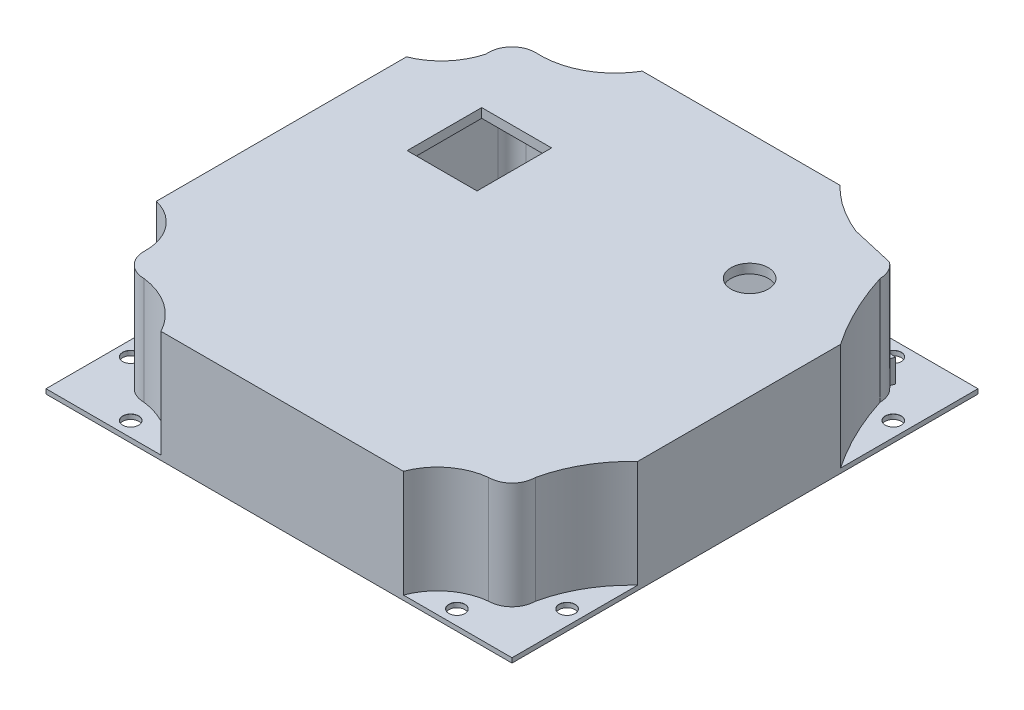
SolidWorks part; units mm, degrees
note: The reader was unsure of these and kept them because the rebuilt part matched: shared geometry of "Sketch21<3>".
material "6061 Alloy"
ref_plane "Front Plane" through (0, 0, 0) normal (0, 0, 1) x (1, 0, 0)
ref_plane "Top Plane" through (0, 0, 0) normal (0, 1, 0) x (1, 0, 0)
ref_plane "Right Plane" through (0, 0, 0) normal (1, 0, 0) x (0, 0, -1)
sketch "Sketch1" plane through (0, 0, 0) normal (0, 1, 0) x (1, 0, 0)
  line L1 (-50, -50) -> (50, -50)
  line L2 (-50, -50) -> (-50, 50)
  line L3 (-50, 50) -> (50, 50)
  line L4 (50, -50) -> (50, 50)
  line L5 (-50, -50) -> (50, 50) construction
  line L6 (-50, 50) -> (50, -50) construction
extrude "Boss-Extrude3" add sketch "Sketch1" along normal blind 6.35
sketch "Sketch8" plane through (0, 6.35, 0) normal (0, 1, 0) x (1, 0, 0)
  line L0 (-50, -50) -> (-39.5, -50)
  line L1 (-50, -50) -> (50, -50) construction
  line L2 (-39.5, -50) -> (-39.5, -39.5)
  line L3 (50, -50) -> (39.5, -50)
  line L4 (39.5, -50) -> (39.5, -39.5)
  line L5 (50, 50) -> (39.5, 50)
  line L6 (-50, 50) -> (50, 50) construction
  line L7 (39.5, 50) -> (39.5, 39.5)
  line L8 (-50, 50) -> (-39.5, 50)
  line L9 (-50, -50) -> (-50, 50) construction
  line L10 (-39.5, 50) -> (-39.5, 39.5)
sketch "Sketch13" plane through (0, 6.35, 0) normal (0, 1, 0) x (1, 0, 0)
  line L1 (-50, -50) -> (-35, -50)
  line L2 (-50, -50) -> (50, -50) construction
  line L3 (-35, -50) -> (-35, -46.825)
  line L4 (-50, -50) -> (-50, -35)
  line L5 (-50, -50) -> (-50, 50) construction
  line L6 (-50, -35) -> (-46.825, -35)
  line L7 (-50, 50) -> (-35, 50)
  line L8 (-50, 50) -> (50, 50) construction
  line L9 (-35, 50) -> (-35, 46.825)
  line L10 (-50, 50) -> (-50, 35)
  line L11 (-50, 35) -> (-46.825, 35)
  line L13 (50, 50) -> (35, 50)
  line L14 (35, 50) -> (35, 46.825)
  line L15 (50, 50) -> (50, 35)
  line L16 (50, -50) -> (50, 50) construction
  line L17 (50, 35) -> (46.825, 35)
  line L18 (50, -50) -> (50, -35)
  line L19 (50, -35) -> (46.825, -35)
  line L20 (50, -50) -> (35, -50)
  line L21 (35, -50) -> (35, -46.825)
hole_wizard "M3 Clearance Hole1" positions "Sketch17" profile "Sketch18" hole size "M3" standard "ANSI Metric" end condition through all
sketch "Sketch17" plane through (0, 6.35, 0) normal (0, 1, 0) x (1, 0, 0)
  point P0 (-46.825, 35)
  point P3 (-35, 46.825)
  point P6 (35, 46.825)
  point P9 (46.825, 35)
  point P12 (46.825, -35)
  point P15 (35, -46.825)
  point P18 (-35, -46.825)
  point P21 (-46.825, -35)
sketch "Sketch18" plane through (-46.825, 6.35, -35) normal (1, 0, 0) x (0, 0, 1)
  line L0 (0, 0) -> (0, 6.35)
  line L1 (0, 6.35) -> (1.7, 6.35)
  line L2 (1.7, 6.35) -> (1.7, 0.025)
  line L3 (1.7, 0.025) -> (1.725, 0)
  line L5 (1.725, 0) -> (0, 0)
  line L6 (-1.7, 0.025) -> (-1.725, 0) construction
  line L11 (0, -6.35) -> (0, 107.95) construction
  dimension "Thru Hole Dia." = 3.4
  dimension "Thru Hole Depth" = 6.35
  dimension "Near C'Sink Dia." = 3.45
  dimension "Near C'Sink Angle" = 90
sketch "Sketch19" plane through (0, 6.35, 0) normal (0, 1, 0) x (1, 0, 0)
  line L1 (-37, -40) -> (37, -40)
  line L2 (-40, -37) -> (-40, 37)
  line L3 (-37, 40) -> (37, 40)
  line L4 (40, -37) -> (40, 37)
  line L5 (-40, -40) -> (40, 40) construction
  line L6 (-40, 40) -> (40, -40) construction
  arc A0 (-37, -40) -> (-40, -37) centre (-37, -37) cw
  arc A1 (40, -37) -> (37, -40) centre (37, -37) cw
  arc A2 (37, 40) -> (40, 37) centre (37, 37) cw
  arc A3 (-37, 40) -> (-40, 37) centre (-37, 37) ccw
  point P0 (0, 0)
  dimension "D1" = 3
extrude "Cut-Extrude1" cut sketch "Sketch19" against normal blind 10
sketch "Sketch20" plane through (0, 6.35, -6.35) normal (0, -1, 0) x (1, 0, 0)
  line L2 (6.2004, 36.4882) -> (20.6711, -21.587) construction
  line L4 (20.6711, -21.587) -> (17.5137, -18.2418) construction
  line L5 (1.6004, 36.4882) -> (1.6004, 46.35)
  line L6 (-37, 46.35) -> (37, 46.35) construction
  line L7 (10.8004, 36.4882) -> (10.8004, 46.35)
  line L8 (23.8395, -18.2522) -> (39.1213, -32.7713)
  line L9 (17.5038, -24.9228) -> (26.6951, -33.65)
  line L10 (37, -33.65) -> (-37, -33.65) construction
  line L18 (1.6004, 46.35) -> (1.6004, 51.4058)
  line L19 (1.6004, 51.4058) -> (10.8004, 51.4058)
  line L20 (10.8004, 51.4058) -> (10.8004, 46.35)
  line L21 (26.6951, -33.65) -> (30.5647, -36.8517)
  line L22 (30.5647, -36.8517) -> (40.2934, -35.6218)
  line L23 (40.2934, -35.6218) -> (39.1213, -32.7713)
  line L25 (1.6065, 36.2521) -> (6.2004, 36.4882) construction
  arc A1 (23.8395, -18.2522) -> (17.5038, -24.9228) centre (20.6711, -21.587) ccw
  arc A2 (1.6004, 36.4882) -> (10.8004, 36.4882) centre (6.2004, 36.4882) ccw
  circle A3 centre (20.6711, -21.587) radius 1.6
  circle A4 centre (6.2004, 36.4882) radius 1.6
  circle A9 centre (6.2004, 36.4882) radius 4.6 construction
  arc A10 (37, -33.65) -> (40, -30.65) centre (37, -30.65) ccw construction
  circle A11 centre (20.6711, -21.587) radius 4.6 construction
  dimension "D2" = 58.0752
  dimension "D5" = 3
extrude "Boss-Extrude4" add sketch "Sketch20" against normal blind 5 contours A3 | A4 | L20 L7 A2 L5 L18 L19 | L23 L8 A1 L9 L21 L22
sketch "Sketch21" plane through (0, 6.35, 0) normal (0, 1, 0) x (1, 0, 0)
  line L2 (40, -37) -> (40, 37) construction
  line L3 (26.6951, 40) -> (-37, 40) construction
  line L4 (-40, 37) -> (-40, -37) construction
  line L7 (40, -37) -> (40, 37)
  line L8 (26.6951, 40) -> (-37, 40)
  line L9 (-40, 37) -> (-40, -37)
  line L10 (-35.0509, 42) -> (-37, 42)
  line L11 (-42, 37) -> (-42, 36.3352)
  line L12 (40.2934, 41.9718) -> (39.1213, 39.1213) construction
  line L13 (30.5647, 43.2017) -> (39.9185, 41.0599)
  line L15 (-50, -50) -> (-50, 50) construction
  line L16 (-50, -50) -> (50, -50) construction
  line L17 (50, -50) -> (50, 50) construction
  line L18 (26.6951, 40) -> (30.5647, 43.2017) construction
  line L19 (-50, 50) -> (50, 50) construction
  line L20 (-22.05, 50) -> (20.3723, 50)
  line L22 (-37, -40) -> (37, -40)
  line L23 (50, 20.5088) -> (50, -23.0373)
  line L24 (26.6951, -50) -> (-25.3277, -50)
  line L25 (-50, -26.3149) -> (-50, 27.345)
  line L26 (-42, -36.1865) -> (-42, -37)
  line L27 (-42, 37) -> (-42, -37) construction
  line L28 (26.6951, 42) -> (-37, 42) construction
  line L29 (42, -37) -> (42, 37) construction
  line L30 (10.8004, -42) -> (37, -42) construction
  line L31 (-37, -42) -> (1.6004, -42) construction
  line L32 (26.6951, 40) -> (39.1213, 39.1213)
  line L35 (10.8004, -40) -> (37, -40) construction
  line L36 (-37, -40) -> (1.6004, -40) construction
  arc A0 (-40, -37) -> (-37, -40) centre (-37, -37) ccw construction
  arc A1 (37, -40) -> (40, -37) centre (37, -37) ccw construction
  arc A2 (40, 37) -> (39.1213, 39.1213) centre (37, 37) ccw construction
  arc A3 (-37, 40) -> (-40, 37) centre (-37, 37) ccw construction
  arc A4 (-40, -37) -> (-37, -40) centre (-37, -37) ccw
  arc A5 (37, -40) -> (40, -37) centre (37, -37) ccw
  arc A6 (40, 37) -> (39.1213, 39.1213) centre (37, 37) ccw
  arc A7 (-37, 40) -> (-40, 37) centre (-37, 37) ccw
  arc A8 (-37, 42) -> (-42, 37) centre (-37, 37) ccw
  arc A9 (-42, -37) -> (-37, -42) centre (-37, -37) ccw
  arc A10 (37, -42) -> (42, -37) centre (37, -37) ccw
  arc A11 (42, 37) -> (39.9185, 41.0599) centre (37, 37) ccw
  arc A12 (-42, 36.3352) -> (-50, 27.345) centre (-55.0701, 39.9113) cw
  arc A13 (-42, -37) -> (-50, -26.3149) centre (-52.5924, -36.5932) ccw
  arc A14 (37, -42) -> (26.6951, -50) centre (38.3269, -54.3462) ccw
  arc A15 (42, -37) -> (50, -23.0373) centre (68.4235, -42.8663) cw
  arc A16 (42, 37) -> (50, 20.5088) centre (102.0026, 55.9216) ccw
  arc A17 (30.5647, 43.2017) -> (20.3723, 50) centre (41.5686, 70.7392) cw
  arc A18 (-37, 42) -> (-22.05, 50) centre (-36.0255, 58.1477) ccw
  arc A19 (-37, -42) -> (-25.3277, -50) centre (-38.8156, -57.1642) cw
  arc A20 (42, 37) -> (40.5355, 40.5355) centre (37, 37) ccw construction
  line M6 (26.6951, 40) -> (30.5647, 43.2017)
  line M8 (40.2934, 41.9718) -> (39.1213, 39.1213)
  arc M9 (39.1213, 39.1213) -> (40, 37) centre (37, 37) cw
  line M10 (40, 37) -> (40, -37)
  arc M11 (40, -37) -> (37, -40) centre (37, -37) cw
  line M12 (37, -40) -> (10.8004, -40)
  line M13 (10.8004, -40) -> (10.8004, -45.0558)
  line M14 (10.8004, -45.0558) -> (1.6004, -45.0558)
  line M15 (1.6004, -45.0558) -> (1.6004, -40)
  line M16 (1.6004, -40) -> (-37, -40)
  arc M17 (-37, -40) -> (-40, -37) centre (-37, -37) cw
  line M18 (-40, -37) -> (-40, 37)
  arc M19 (-40, 37) -> (-37, 40) centre (-37, 37) cw
  line M20 (-37, 40) -> (26.6951, 40)
  line M29 (-50, -50) -> (50, -50)
  line M30 (50, -50) -> (50, 50)
  line M31 (50, 50) -> (-50, 50)
  line M32 (-50, 50) -> (-50, -50)
  dimension "D1" = 2
extrude "Boss-Extrude5" add sketch "Sketch21" along normal up to surface (5 mm away) contours A9 A19 A14 A10 A15 A16 A11 A17 A18 A8 L11 A12 A13 M29 M30 M8 M9 M10 M11 M12 M13 M14 M15 M16 M17 M18 M19 M20 M6 M31 M32 | L32 L13 M6 M8 | L22 M15 M14 M13 up to face at (20.6711, 11.35, -26.337)
extrude "Boss-Extrude6" add sketch "Sketch21<3>" along normal blind 16 from surface at 5 contours A9 A19 A14 A10 A15 A16 A11 A17 A18 A8 L11 A12 A13 M29 M30 M8 M9 M10 M11 M12 M13 M14 M15 M16 M17 M18 M19 M20 M6 M31 M32 | L32 L13 M6 M8 | L22 M15 M14 M13 starting at face at (6.081, 11.35, 2.9588)
sketch "Sketch21<3>" plane through (0, 6.35, 0) normal (0, 1, 0) x (1, 0, 0) same geometry as "Sketch21"
sketch "Sketch22" plane through (0, 27.35, 0) normal (0, 1, 0) x (1, 0, 0)
  line L0 (28, 40) -> (28, 23) construction
  line L1 (-37, 40) -> (26.6951, 40) construction
  line L2 (28, 23) -> (40, 23) construction
  line L3 (40, 37) -> (40, -37) construction
  line L4 (-32.5, 40) -> (-32.5, 26) construction
  line L5 (-32.5, 26) -> (-40, 26) construction
  line L6 (-42, 37) -> (-42, 36.3352)
  line L7 (-50, 27.345) -> (-50, -26.3149)
  line L8 (-25.3277, -50) -> (26.6951, -50)
  line L9 (50, -23.0373) -> (50, 20.5088)
  line L10 (39.9185, 41.0599) -> (30.5647, 43.2017)
  line L11 (20.3723, 50) -> (-22.05, 50)
  line L12 (-42, 37) -> (-42, 36.3352)
  line L13 (-50, 27.345) -> (-50, -26.3149)
  line L14 (-25.3277, -50) -> (26.6951, -50)
  line L15 (50, -23.0373) -> (50, 20.5088)
  line L16 (39.9185, 41.0599) -> (30.5647, 43.2017)
  line L17 (20.3723, 50) -> (-22.05, 50)
  line L18 (-40, -37) -> (-40, 37) construction
  line L19 (-32.5, 26) -> (-32.5, 10)
  line L20 (-32.5, 10) -> (-17.5, 10)
  line L21 (-17.5, 10) -> (-17.5, 26)
  line L22 (-17.5, 26) -> (-32.5, 26)
  circle A0 centre (28, 23) radius 4
  arc A12 (-37, 42) -> (-42, 37) centre (-37, 37) ccw
  arc A13 (-50, 27.345) -> (-42, 36.3352) centre (-55.0701, 39.9113) ccw
  arc A14 (-42, -37) -> (-50, -26.3149) centre (-52.5924, -36.5932) ccw
  arc A15 (-42, -37) -> (-37, -42) centre (-37, -37) ccw
  arc A16 (-25.3277, -50) -> (-37, -42) centre (-38.8156, -57.1642) ccw
  arc A17 (37, -42) -> (26.6951, -50) centre (38.3269, -54.3462) ccw
  arc A18 (37, -42) -> (42, -37) centre (37, -37) ccw
  arc A19 (50, -23.0373) -> (42, -37) centre (68.4235, -42.8663) ccw
  arc A20 (42, 37) -> (50, 20.5088) centre (102.0026, 55.9216) ccw
  arc A21 (42, 37) -> (39.9185, 41.0599) centre (37, 37) ccw
  arc A22 (20.3723, 50) -> (30.5647, 43.2017) centre (41.5686, 70.7392) ccw
  arc A23 (-37, 42) -> (-22.05, 50) centre (-36.0255, 58.1477) ccw
  arc A24 (-37, 42) -> (-42, 37) centre (-37, 37) ccw
  arc A25 (-50, 27.345) -> (-42, 36.3352) centre (-55.0701, 39.9113) ccw
  arc A26 (-42, -37) -> (-50, -26.3149) centre (-52.5924, -36.5932) ccw
  arc A27 (-42, -37) -> (-37, -42) centre (-37, -37) ccw
  arc A28 (-25.3277, -50) -> (-37, -42) centre (-38.8156, -57.1642) ccw
  arc A29 (37, -42) -> (26.6951, -50) centre (38.3269, -54.3462) ccw
  arc A30 (37, -42) -> (42, -37) centre (37, -37) ccw
  arc A31 (50, -23.0373) -> (42, -37) centre (68.4235, -42.8663) ccw
  arc A32 (42, 37) -> (50, 20.5088) centre (102.0026, 55.9216) ccw
  arc A33 (42, 37) -> (39.9185, 41.0599) centre (37, 37) ccw
  arc A34 (20.3723, 50) -> (30.5647, 43.2017) centre (41.5686, 70.7392) ccw
  arc A35 (-37, 42) -> (-22.05, 50) centre (-36.0255, 58.1477) ccw
  dimension "D4" = 8
  dimension "D2" = 17
  dimension "D3" = 12
  dimension "D5" = 14
  dimension "D6" = 7.5
  dimension "D7" = 16
  dimension "D8" = 15
  dimension "D1" = 0
extrude "Boss-Extrude7" add sketch "Sketch22" along normal blind 2
sketch "Sketch24" plane through (0, 0, 0) normal (0, -1, 0) x (1, 0, 0)
  line L4 (-40, 37) -> (-40, -37)
  line L5 (37, 40) -> (-37, 40)
  line L6 (40, -37) -> (40, 37)
  line L7 (-37, -40) -> (37, -40)
  line L8 (-40, 37) -> (-40, -37)
  line L9 (37, 40) -> (-37, 40)
  line L10 (40, -37) -> (40, 37)
  line L11 (-37, -40) -> (37, -40)
  line L12 (50, 50) -> (-50, 50)
  line L13 (-50, 50) -> (-50, -50)
  line L14 (-50, -50) -> (50, -50)
  line L15 (50, -50) -> (50, 50)
  line L16 (50, 50) -> (-50, 50)
  line L17 (-50, 50) -> (-50, -50)
  line L18 (-50, -50) -> (50, -50)
  line L19 (50, -50) -> (50, 50)
  circle A1 centre (-46.825, -35) radius 1.7
  circle A2 centre (-46.825, -35) radius 1.7
  circle A3 centre (-35, -46.825) radius 1.7
  circle A4 centre (-35, -46.825) radius 1.7
  circle A5 centre (35, -46.825) radius 1.7
  circle A6 centre (35, -46.825) radius 1.7
  circle A7 centre (46.825, -35) radius 1.7
  circle A8 centre (46.825, -35) radius 1.7
  circle A9 centre (46.825, 35) radius 1.7
  circle A10 centre (46.825, 35) radius 1.7
  circle A11 centre (35, 46.825) radius 1.7
  circle A12 centre (35, 46.825) radius 1.7
  circle A13 centre (-35, 46.825) radius 1.7
  circle A14 centre (-35, 46.825) radius 1.7
  circle A15 centre (-46.825, 35) radius 1.7
  circle A16 centre (-46.825, 35) radius 1.7
  arc A20 (-37, 40) -> (-40, 37) centre (-37, 37) ccw
  arc A21 (40, 37) -> (37, 40) centre (37, 37) ccw
  arc A22 (37, -40) -> (40, -37) centre (37, -37) ccw
  arc A23 (-40, -37) -> (-37, -40) centre (-37, -37) ccw
  arc A24 (-37, 40) -> (-40, 37) centre (-37, 37) ccw
  arc A25 (40, 37) -> (37, 40) centre (37, 37) ccw
  arc A26 (37, -40) -> (40, -37) centre (37, -37) ccw
  arc A27 (-40, -37) -> (-37, -40) centre (-37, -37) ccw
  dimension "D1" = 0
  dimension "D2" = 0
  dimension "D3" = 0
  dimension "D4" = 0
  dimension "D5" = 0
  dimension "D6" = 0
  dimension "D7" = 0
  dimension "D8" = 0
  dimension "D9" = 0
  dimension "D10" = 0
extrude "Cut-Extrude2" cut sketch "Sketch24" against normal offset from surface (5.35 mm away) 1 up to face at (-35, 6.35, 48.55)
sketch "Sketch25" plane through (0, 6.35, 0) normal (0, -1, 0) x (1, 0, 0)
  line L3 (10.8004, 40) -> (1.6004, 40)
  line L4 (1.6004, 40) -> (1.6004, 30.1382)
  line L5 (10.8004, 30.1382) -> (10.8004, 40)
  line L6 (10.8004, 40) -> (1.6004, 40)
  line L7 (1.6004, 40) -> (1.6004, 30.1382)
  line L8 (10.8004, 30.1382) -> (10.8004, 40)
  line L9 (39.1213, -39.1213) -> (23.8395, -24.6022)
  line L10 (17.5038, -31.2728) -> (26.6951, -40)
  line L11 (26.6951, -40) -> (37, -40)
  line L12 (39.1213, -39.1213) -> (23.8395, -24.6022)
  line L13 (17.5038, -31.2728) -> (26.6951, -40)
  line L14 (26.6951, -40) -> (37, -40)
  arc A1 (1.6004, 30.1382) -> (10.8004, 30.1382) centre (6.2004, 30.1382) ccw
  arc A2 (1.6004, 30.1382) -> (10.8004, 30.1382) centre (6.2004, 30.1382) ccw
  arc A4 (37, -40) -> (39.1213, -39.1213) centre (37, -37) ccw
  arc A5 (23.8395, -24.6022) -> (17.5038, -31.2728) centre (20.6711, -27.937) ccw
  arc A6 (37, -40) -> (39.1213, -39.1213) centre (37, -37) ccw
  arc A7 (23.8395, -24.6022) -> (17.5038, -31.2728) centre (20.6711, -27.937) ccw
  dimension "D1" = 0
  dimension "D2" = 0
extrude "Cut-Extrude3" cut sketch "Sketch25" against normal blind 5
